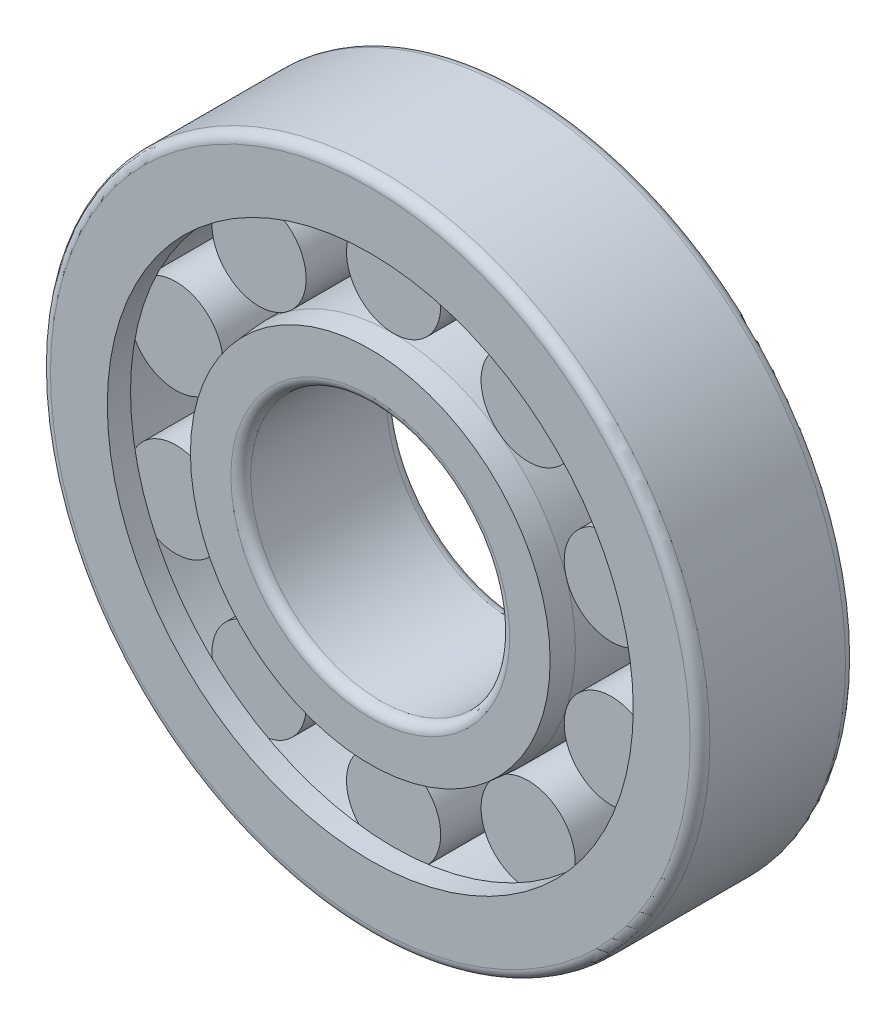
SolidWorks part; units mm, degrees
ref_plane "Front Plane" through (0, 0, 0) normal (0, 0, 1) x (1, 0, 0)
ref_plane "Top Plane" through (0, 0, 0) normal (0, 1, 0) x (1, 0, 0)
ref_plane "Right Plane" through (0, 0, 0) normal (1, 0, 0) x (0, 0, -1)
sketch "BaseSke" plane through (0, 0, 0) normal (1, 0, 0) x (0, 0, -1)
  line L0 (-47.2296, 0) -> (24.6132, 0) construction
  line L1 (-47.2296, 48.6) -> (24.6132, 48.6) construction
  line L2 (0, 129.5214) -> (0, -86.3012) construction
  line L3 (-11.55, 48.6) -> (-11.55, 58.6) construction
  line L4 (-16.5, 70) -> (16.5, 70) construction
  line L5 (-16.5, 27.5) -> (16.5, 27.5) construction
  line L6 (-11.55, 38.6) -> (11.55, 38.6)
  line L7 (-11.55, 38.6) -> (-11.55, 48.6)
  line L8 (-11.55, 48.6) -> (11.55, 48.6)
  line L9 (11.55, 38.6) -> (11.55, 48.6)
  line L10 (-11.55, 58.6) -> (11.55, 58.6) construction
  line L11 (11.55, 58.6) -> (11.55, 48.6) construction
  dimension "D2" = 23.1
  dimension "Diameter_Ew" = 117.2
revolve "Roller" add sketch "BaseSke" angle 360 about L8
sketch "OuterRaceSke" plane through (0, 0, 0) normal (1, 0, 0) x (0, 0, -1)
  line L0 (0, 0) -> (0, 87.5396) construction
  line L1 (-16.5, 70) -> (16.5, 70)
  line L2 (-16.5, 70) -> (-16.5, 55.8333)
  line L3 (-16.5, 55.8333) -> (-11.575, 55.8333)
  line L4 (16.5, 70) -> (16.5, 55.8333)
  line L5 (-50.3916, 0) -> (55.2197, 0) construction
  line L6 (-11.55, 58.6) -> (11.55, 58.6) construction
  line L7 (11.575, 55.8333) -> (16.5, 55.8333)
  line L9 (-11.575, 55.8333) -> (-11.575, 58.58)
  line L10 (-11.575, 58.58) -> (11.575, 58.58)
  line L11 (11.575, 55.8333) -> (11.575, 58.58)
  dimension "D2" = 111.6667
  dimension "D1" = 23.15
  dimension "D3" = 0.02
revolve "OuterRace" add sketch "OuterRaceSke" angle 360 about L5
sketch "InnerRaceSke" plane through (0, 0, 0) normal (1, 0, 0) x (0, 0, -1)
  line L0 (-70.8626, 0) -> (113.5527, 0) construction
  line L1 (0, 58.441) -> (0, -70.8113) construction
  line L2 (-16.5, 27.5) -> (16.5, 27.5)
  line L3 (-16.5, 27.5) -> (-16.5, 41.6667)
  line L4 (-11.575, 41.6667) -> (-11.575, 38.62)
  line L5 (-11.575, 41.6667) -> (-16.5, 41.6667)
  line L6 (0, 129.5214) -> (0, -86.3012) construction
  line L7 (-11.575, 38.62) -> (11.575, 38.62)
  line L9 (16.5, 27.5) -> (16.5, 41.6667)
  line L10 (11.575, 41.6667) -> (16.5, 41.6667)
  line L11 (11.575, 38.62) -> (11.575, 41.6667)
  line L13 (-11.55, 38.6) -> (11.55, 38.6) construction
  point P17 (0, 27.5)
  dimension "D1" = 23.15
  dimension "D2" = 0.02
  dimension "D3" = 83.3333
revolve "InnerRace" add sketch "InnerRaceSke" angle 360 about L0
fillet "Fillet1" radius 2.1 4 edges at (27.5, 0, 16.5) (70, 0, -16.5) (70, 0, 16.5) (27.5, 0, -16.5)
sketch "NFSke" plane through (0, 0, 0) normal (1, 0, 0) x (0, 0, -1)
  line L0 (-54.6114, 0) -> (63.7655, 0) construction
  line L1 (16.5, 59.0109) -> (11.575, 58.58)
  line L2 (11.575, 58.58) -> (11.575, 55.8333)
  line L3 (11.575, 55.8333) -> (16.5, 55.8333)
  line L4 (16.5, 55.8333) -> (16.5, 59.0109)
  dimension "D1" = 5
revolve "NF" [suppressed] cut sketch "NFSke" angle 360 about L0
mirror "N" [suppressed] about plane through (0, 0, 0) normal (0, 0, 1)
sketch "NJSke" plane through (0, 0, 0) normal (1, 0, 0) x (0, 0, -1)
  line L0 (-35.6078, 0) -> (44.429, 0) construction
  line L1 (16.5, 41.6667) -> (11.575, 41.6667)
  line L2 (11.575, 41.6667) -> (11.575, 38.62)
  line L3 (11.575, 38.62) -> (16.5, 38.1891)
  line L4 (16.5, 38.1891) -> (16.5, 41.6667)
  dimension "D1" = 5
revolve "NJ" cut sketch "NJSke" angle 360 about L0
mirror "NU" about plane through (0, 0, 0) normal (0, 0, 1) of "NJ"
pattern_circular "CirPatternBall" count 10 over 360 about axis through (0, 0, 50.3916) along (0, 0, -1) of "Roller"
sketch "SimplifiedSke" plane through (0, 0, 0) normal (1, 0, 0) x (0, 0, -1)
  line L0 (37.5911, 0) -> (-37.5911, 0) construction
  line L1 (-13.1351, 48.6) -> (13.151, 48.6) construction
  line L2 (-11.55, 58.6) -> (11.55, 58.6)
  line L3 (-11.55, 58.6) -> (-11.55, 38.6)
  line L4 (-11.55, 38.6) -> (11.55, 38.6)
  line L5 (11.55, 58.6) -> (11.55, 38.6)
  line L6 (-47.2296, 48.6) -> (24.6132, 48.6) construction
revolve "Simplified" [suppressed] add sketch "SimplifiedSke" angle 360 about L0
equation "\"D2@BaseSke\" = \"Bearing_Thickness@BaseSke\"*0.7"
equation "\"D1@OuterRaceSke\" = \"Bearing_Thickness@BaseSke\"*0.7+0.05"
equation "\"D2@OuterRaceSke\" =\"Bearing_Outside_Diameter@BaseSke\" -  ( \"Bearing_Outside_Diameter@BaseSke\" - \"Bearing_Inside_Diameter@BaseSke\"  )/ 3 "
equation "\"D1@InnerRaceSke\" = \"Bearing_Thickness@BaseSke\"*0.7+0.05"
equation "\"D3@InnerRaceSke\" = \"Bearing_Inside_Diameter@BaseSke\" +  ( \"Bearing_Outside_Diameter@BaseSke\" - \"Bearing_Inside_Diameter@BaseSke\" ) / 3 "
equation "\"D1@CirPatternBall\" =  int(  ( \"Bearing_Outside_Diameter@BaseSke\" + \"Bearing_Inside_Diameter@BaseSke\" )  / 2 *  pi  /  ( \"Bearing_Outside_Diameter@BaseSke\" - \"Bearing_Inside_Diameter@BaseSke\" ) * 3 ) "
